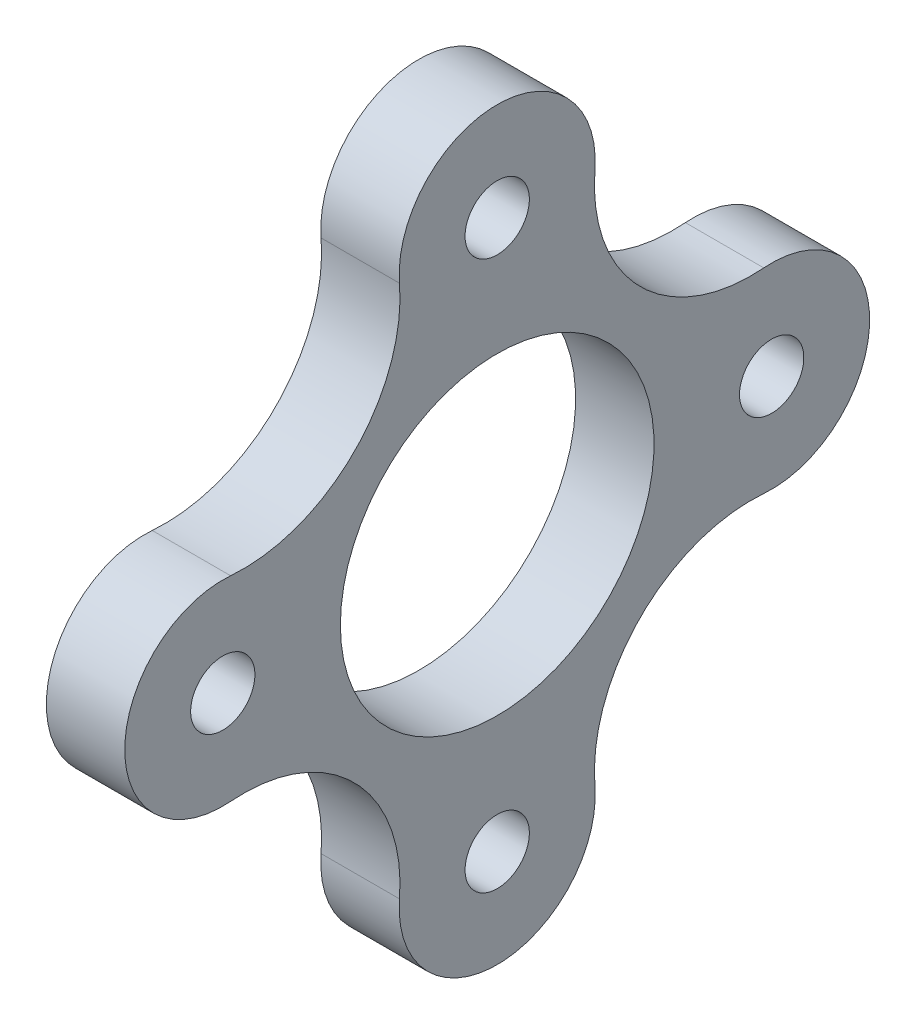
SolidWorks part; units mm, degrees
ref_plane "Front Plane" through (0, 0, 0) normal (0, 0, 1) x (1, 0, 0)
ref_plane "Top Plane" through (0, 0, 0) normal (0, 1, 0) x (1, 0, 0)
ref_plane "Right Plane" through (0, 0, 0) normal (1, 0, 0) x (0, 0, -1)
sketch "Sketch1" plane through (33.3375, 0, 0) normal (-1, 0, 0) x (0, 0, 1)
  line L0 (0, 187.45) -> (22.225, 187.45) construction
  line L1 (22.225, 187.45) -> (30.1625, 187.45) construction
  line L2 (0, 165.225) -> (0, 157.2875) construction
  circle A0 centre (0, 187.45) radius 12.7 construction
  circle A1 centre (0, 187.45) radius 12.7
  circle A2 centre (22.225, 187.45) radius 2.6035
  circle A3 centre (0, 165.225) radius 2.6035
  circle A4 centre (-22.225, 187.45) radius 2.6035
  circle A5 centre (0, 209.675) radius 2.6035
  arc A7 (30.1625, 187.45) -> (21.5889, 179.538) centre (22.225, 187.45) cw
  arc A8 (0, 157.2875) -> (7.912, 165.8611) centre (0, 165.225) ccw
  arc A9 (7.912, 165.8611) -> (21.5889, 179.538) centre (20.5711, 166.8789) cw
  arc A10 (-30.1625, 187.45) -> (-21.5889, 179.538) centre (-22.225, 187.45) ccw
  arc A11 (-21.5889, 179.538) -> (-7.912, 165.8611) centre (-20.5711, 166.8789) cw
  arc A12 (0, 157.2875) -> (-7.912, 165.8611) centre (0, 165.225) cw
  arc A13 (0, 217.6125) -> (-7.912, 209.0389) centre (0, 209.675) ccw
  arc A14 (-7.912, 209.0389) -> (-21.5889, 195.362) centre (-20.5711, 208.0211) cw
  arc A15 (-30.1625, 187.45) -> (-21.5889, 195.362) centre (-22.225, 187.45) cw
  arc A16 (30.1625, 187.45) -> (21.5889, 195.362) centre (22.225, 187.45) ccw
  arc A17 (21.5889, 195.362) -> (7.912, 209.0389) centre (20.5711, 208.0211) cw
  arc A18 (0, 217.6125) -> (7.912, 209.0389) centre (0, 209.675) cw
  point P14 (0, 187.45)
  point P41 (0, 187.45)
  dimension "D3" = 5.207
  dimension "D4" = 7.9375
  dimension "D5" = 12.7
  dimension "D1" = 22.225
  dimension "D2" = 4
  dimension "D6" = 4
extrude "Boss-Extrude1" add sketch "Sketch1" along normal blind 6.35
